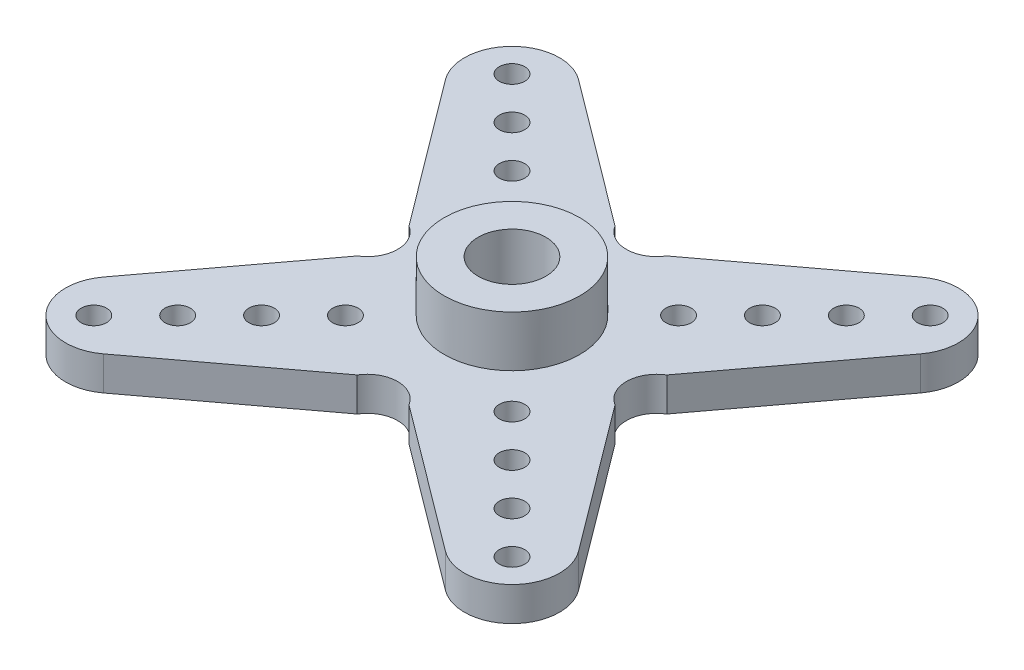
SolidWorks part; units mm, degrees
ref_plane "Front Plane" through (0, 0, 0) normal (0, 0, 1) x (1, 0, 0)
ref_plane "Top Plane" through (0, 0, 0) normal (0, 1, 0) x (1, 0, 0)
ref_plane "Right Plane" through (0, 0, 0) normal (1, 0, 0) x (0, 0, -1)
sketch "Sketch1" plane through (0, 0, 0) normal (0, 1, 0) x (1, 0, 0)
  line L1 (-16.5732, 5.6349) -> (10.9332, 5.6349) construction
  line L2 (-2.82, 5.6349) -> (-2.82, -21.8715) construction
  line L3 (10.9332, -21.8715) -> (-16.5732, -21.8715) construction
  line L4 (10.9332, 5.6349) -> (10.9332, -21.8715) construction
  line L5 (-10.4267, -6.5927) -> (-4.3456, -0.5116) construction
  line L6 (-16.5732, 5.6349) -> (10.9332, -21.8715) construction
  line L7 (-16.2904, -8.1183) -> (10.9332, -8.1183) construction
  line L8 (11.1955, 1.9694) -> (4.7867, -6.5927)
  line L9 (7.2676, 5.8972) -> (-1.2945, -0.5116)
  line L10 (4.7867, -6.5927) -> (-1.2945, -0.5116) construction
  line L11 (-16.8355, -18.2059) -> (-10.4267, -9.6438)
  line L12 (-12.9077, -22.1338) -> (-4.3456, -15.725)
  line L13 (-12.9077, 5.8972) -> (-4.3456, -0.5116)
  line L14 (-16.8355, 1.9694) -> (-10.4267, -6.5927)
  line L15 (-16.5732, -21.8715) -> (10.9332, 5.6349) construction
  line L19 (7.2676, -22.1338) -> (-1.2945, -15.725)
  line L20 (11.1955, -18.2059) -> (4.7867, -9.6438)
  circle A0 centre (-2.82, -8.1183) radius 6.75 construction
  arc A1 (-10.4267, -6.5927) -> (-10.4267, -9.6438) centre (-11.3567, -8.1183) cw
  arc A2 (11.1955, -18.2059) -> (7.2676, -22.1338) centre (8.9491, -19.8874) cw
  arc A3 (-16.8355, 1.9694) -> (-12.9077, 5.8972) centre (-14.5891, 3.6508) cw
  arc A4 (11.1955, 1.9694) -> (7.2676, 5.8972) centre (8.9491, 3.6508) ccw
  arc A5 (4.7867, -6.5927) -> (4.7867, -9.6438) centre (5.7167, -8.1183) ccw
  arc A6 (-16.8355, -18.2059) -> (-12.9077, -22.1338) centre (-14.5891, -19.8874) ccw
  arc A7 (-1.2945, -15.725) -> (-4.3456, -15.725) centre (-2.82, -16.655) ccw
  arc A8 (-1.2945, -0.5116) -> (-4.3456, -0.5116) centre (-2.82, 0.4184) cw
  point P6 (10.9332, -8.1183)
  point P7 (-2.82, 5.6349)
  dimension "D1" = 19.45
  dimension "D4" = 8.6
extrude "Boss-Extrude1" add sketch "Sketch1" along normal blind 2
sketch "Sketch5" plane through (0, 2, 0) normal (0, 1, 0) x (1, 0, 0)
  circle A4 centre (-2.82, -8.1183) radius 4
  circle A5 centre (-2.82, -8.1183) radius 1.9985
  circle A6 centre (-2.82, -8.1183) radius 6.75 construction
  dimension "D1" = 8
extrude "Boss-Extrude2" add sketch "Sketch5" along normal blind 3
ref_axis "Axis1" through (-2.82, 5, 8.1183) along (0, -1, 0)
sketch "Sketch8" plane through (0, 0, 0) normal (0, -1, 0) x (1, 0, 0)
  circle A0 centre (-2.82, 8.1183) radius 1.5
  dimension "D1" = 3
extrude "Cut-Extrude2" cut sketch "Sketch8" against normal through all
sketch "Sketch9" plane through (0, 0, 0) normal (0, -1, 0) x (1, 0, 0)
  circle A0 centre (-2.82, 8.1183) radius 3.6
  circle A1 centre (-2.82, 8.1183) radius 3
  dimension "D1" = 7.2
  dimension "D2" = 0.6
extrude "Boss-Extrude3" add sketch "Sketch9" along normal blind 0.85
sketch "Sketch10" plane through (0, 0, 0) normal (0, -1, 0) x (1, 0, 0)
  line L0 (-16.5732, 21.8715) -> (10.9332, -5.6349) construction
  circle A0 centre (9.519, -4.2207) radius 0.75
  dimension "D1" = 1.5
  dimension "D2" = 2
extrude "Cut-Extrude3" cut sketch "Sketch10" against normal up to next
pattern_linear "LPattern1" count 4 spacing 3.5 along (-0.7071, 0, 0.7071) of "Cut-Extrude3"
pattern_circular "CirPattern1" count 4 every 90 about axis through (-2.82, 5, 8.1183) along (0, -1, 0) of "LPattern1"
